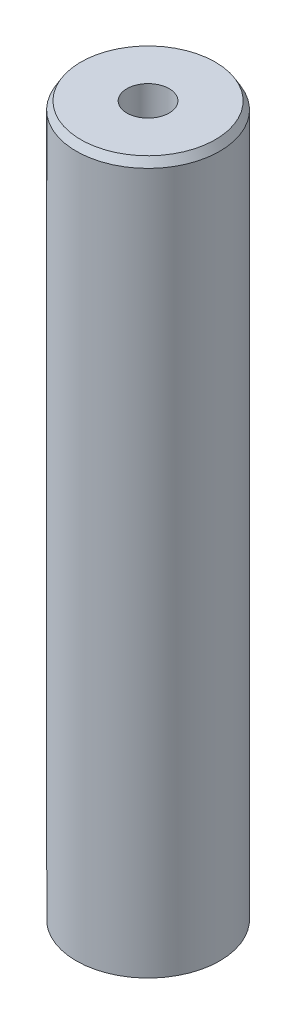
SolidWorks part; units mm, degrees
ref_plane "Front Plane" through (0, 0, 0) normal (0, 0, 1) x (1, 0, 0)
ref_plane "Top Plane" through (0, 0, 0) normal (0, 1, 0) x (1, 0, 0)
ref_plane "Right Plane" through (0, 0, 0) normal (1, 0, 0) x (0, 0, -1)
sketch "Sketch1" plane through (0, 0, 0) normal (0, 1, 0) x (1, 0, 0)
  circle A0 centre (0, 0) radius 17.5
  dimension "SHAFT_OD" = 35
extrude "Boss-Extrude1" add sketch "Sketch1" along normal blind 174.0139
sketch "Sketch2" plane through (0, 0, 0) normal (0, 1, 0) x (1, 0, 0)
  circle A0 centre (0, 0) radius 5.1584
  dimension "BORE_D" = 10.3169
extrude "Cut-Extrude1" cut sketch "Sketch2" along normal through all
chamfer "Chamfer1" distance 1.8969 angle 30 2 edges at (0, 174.0139, 17.5) (0, 0, 17.5) first distance on face at (0, 174.0139, 17.5) first distance on face at (0, 0, 5.1584)
